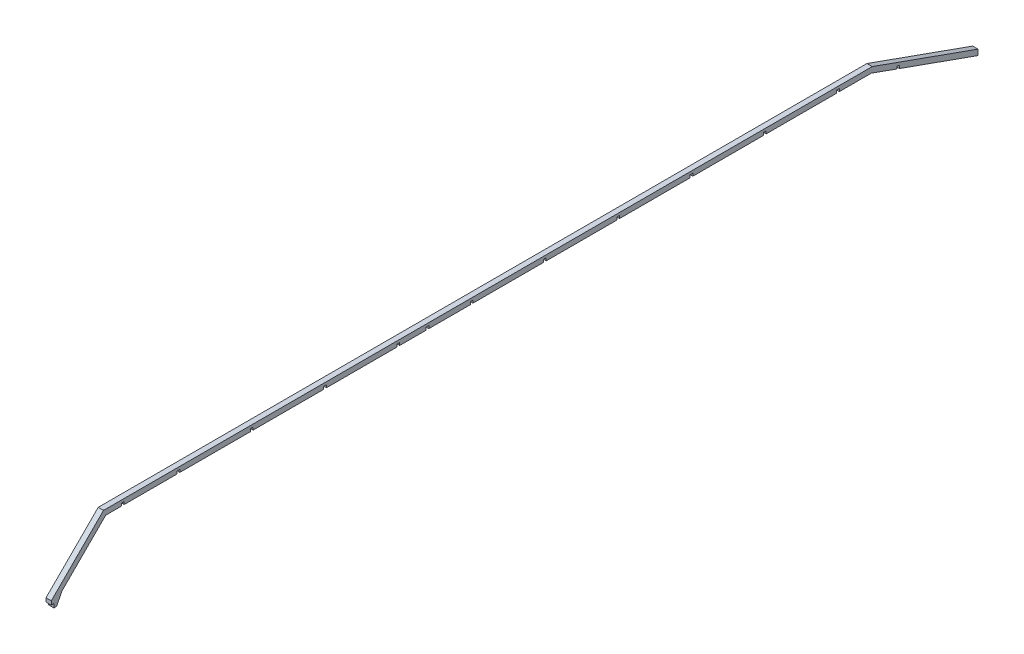
SolidWorks part; units mm, degrees
ref_plane "Спереди" through (0, 0, 0) normal (0, 0, 1) x (1, 0, 0)
ref_plane "Сверху" through (0, 0, 0) normal (0, 1, 0) x (1, 0, 0)
ref_plane "Справа" through (0, 0, 0) normal (1, 0, 0) x (0, 0, -1)
other "Configuration Table"
sketch "Эскиз1" plane through (0, 0, 0) normal (1, 0, 0) x (0, 0, -1)
  line L0 (-751.8866, -19.1422) -> (-733.9606, -19.1422)
  line L1 (115.1734, -19.1422) -> (144.0394, -29.4493)
  line L6 (160.4534, -35.3102) -> (162.4711, -29.6596) construction
  line L7 (-813.5251, -80.7807) -> (-751.8866, -19.1422) construction
  line L8 (-813.5251, -72.2954) -> (-813.5251, -80.7807) construction
  line L13 (-813.5251, -76.538) -> (-810.5251, -76.538)
  line L14 (-813.5251, -76.538) -> (-813.5251, -72.2954)
  line L17 (147.0394, -30.5205) -> (147.0394, -27.5205)
  line L18 (147.0394, -27.5205) -> (144.0394, -26.4493)
  line L19 (144.0394, -26.4493) -> (144.0394, -29.4493)
  line L20 (147.0394, -30.5205) -> (236.0394, -62.2995)
  line L21 (79.0394, -19.1422) -> (79.0394, -16.1422)
  line L22 (79.0394, -16.1422) -> (76.0394, -16.1422)
  line L23 (76.0394, -16.1422) -> (76.0394, -19.1422)
  line L24 (79.0394, -19.1422) -> (115.1734, -19.1422)
  line L25 (-3.9606, -19.1422) -> (-3.9606, -16.1422)
  line L26 (-3.9606, -16.1422) -> (-6.9606, -16.1422)
  line L27 (-6.9606, -16.1422) -> (-6.9606, -19.1422)
  line L28 (-86.9606, -19.1422) -> (-86.9606, -16.1422)
  line L29 (-86.9606, -16.1422) -> (-89.9606, -16.1422)
  line L30 (-89.9606, -16.1422) -> (-89.9606, -19.1422)
  line L31 (-169.9606, -19.1422) -> (-169.9606, -16.1422)
  line L32 (-169.9606, -16.1422) -> (-172.9606, -16.1422)
  line L33 (-172.9606, -16.1422) -> (-172.9606, -19.1422)
  line L34 (-252.9606, -19.1422) -> (-252.9606, -16.1422)
  line L35 (-252.9606, -16.1422) -> (-255.9606, -16.1422)
  line L36 (-255.9606, -16.1422) -> (-255.9606, -19.1422)
  line L37 (-335.9606, -19.1422) -> (-335.9606, -16.1422)
  line L38 (-335.9606, -16.1422) -> (-338.9606, -16.1422)
  line L39 (-338.9606, -16.1422) -> (-338.9606, -19.1422)
  line L40 (-3.9606, -19.1422) -> (76.0394, -19.1422)
  line L41 (-86.9606, -19.1422) -> (-6.9606, -19.1422)
  line L42 (-169.9606, -19.1422) -> (-89.9606, -19.1422)
  line L43 (-252.9606, -19.1422) -> (-172.9606, -19.1422)
  line L44 (-335.9606, -19.1422) -> (-255.9606, -19.1422)
  line L45 (-385.9606, -19.1422) -> (-385.9606, -16.1422)
  line L46 (-385.9606, -16.1422) -> (-388.9606, -16.1422)
  line L47 (-388.9606, -16.1422) -> (-388.9606, -19.1422)
  line L48 (-385.9606, -19.1422) -> (-338.9606, -19.1422)
  line L49 (-418.9606, -19.1422) -> (-418.9606, -16.1422)
  line L50 (-418.9606, -16.1422) -> (-421.9606, -16.1422)
  line L51 (-421.9606, -16.1422) -> (-421.9606, -19.1422)
  line L52 (-418.9606, -19.1422) -> (-388.9606, -19.1422)
  line L53 (-501.9606, -19.1422) -> (-501.9606, -16.1422)
  line L54 (-501.9606, -16.1422) -> (-504.9606, -16.1422)
  line L55 (-504.9606, -16.1422) -> (-504.9606, -19.1422)
  line L56 (-584.9606, -19.1422) -> (-584.9606, -16.1422)
  line L57 (-584.9606, -16.1422) -> (-587.9606, -16.1422)
  line L58 (-587.9606, -16.1422) -> (-587.9606, -19.1422)
  line L59 (-667.9606, -19.1422) -> (-667.9606, -16.1422)
  line L60 (-667.9606, -16.1422) -> (-670.9606, -16.1422)
  line L61 (-670.9606, -16.1422) -> (-670.9606, -19.1422)
  line L62 (-501.9606, -19.1422) -> (-421.9606, -19.1422)
  line L63 (-584.9606, -19.1422) -> (-504.9606, -19.1422)
  line L64 (-667.9606, -19.1422) -> (-587.9606, -19.1422)
  line L65 (-730.9606, -19.1422) -> (-730.9606, -16.1422)
  line L66 (-730.9606, -16.1422) -> (-733.9606, -16.1422)
  line L67 (-733.9606, -16.1422) -> (-733.9606, -19.1422)
  line L68 (-730.9606, -19.1422) -> (-670.9606, -19.1422)
  line L69 (236.0394, -62.2995) -> (238.0571, -56.6489) construction
  line L70 (-3.9606, -19.1422) -> (-3.9606, -13.1422) construction
  line L71 (162.4711, -29.6596) -> (82.2261, -1.0067) construction
  line L72 (238.0571, -56.6489) -> (162.4711, -29.6596) construction
  line L73 (79.0394, -19.1422) -> (79.0394, -13.1422) construction
  line L74 (236.0394, -62.2995) -> (236.0394, -55.9285)
  line L75 (-3.9606, -13.1422) -> (116.2125, -13.1422) construction
  line L76 (-803.8198, -71.0753) -> (-808.0624, -66.8327) construction
  line L77 (-751.8866, -19.1422) -> (-756.1293, -14.8995) construction
  line L78 (-3.9606, -13.1422) -> (-770.7331, -13.1422) construction
  line L79 (-756.1293, -14.8995) -> (-813.5251, -72.2954) construction
  line L80 (-810.5251, -76.538) -> (-810.5251, -80.7807)
  line L81 (-810.5251, -80.7807) -> (-807.5251, -80.7807)
  line L82 (-807.5251, -80.7807) -> (-801.5251, -80.7807) construction
  line L83 (-801.5251, -80.7807) -> (-801.5251, -68.7807) construction
  line L84 (-807.5251, -80.7807) -> (-801.5251, -68.7807)
  line L85 (-801.5251, -68.7807) -> (-751.8866, -19.1422)
  line L86 (-813.5251, -72.2954) -> (-754.3719, -13.1422)
  line L87 (-754.3719, -13.1422) -> (116.2125, -13.1422)
  line L88 (116.2125, -13.1422) -> (236.0394, -55.9285)
  point P49 (-388.9606, -17.6422)
  dimension "D1" = 160.35
  dimension "D2" = 128.34
  dimension "D4" = 6
  dimension "D5" = 6
  dimension "D6" = 867.06
  dimension "D7" = 6
  dimension "D8" = 3
  dimension "D9" = 3
  dimension "D10" = 6
  dimension "D11" = 81.17
  dimension "D12" = 3
  dimension "D13" = 65
  dimension "D14" = 3
  dimension "D15" = 3
  dimension "D16" = 3
  dimension "D17" = 80
  dimension "D18" = 3
  dimension "D19" = 80
  dimension "D20" = 3
  dimension "D21" = 80
  dimension "D22" = 3
  dimension "D23" = 80
  dimension "D24" = 3
  dimension "D25" = 80
  dimension "D26" = 3
  dimension "D27" = 47
  dimension "D28" = 3
  dimension "D29" = 3
  dimension "D30" = 30
  dimension "D31" = 3
  dimension "D32" = 80
  dimension "D33" = 3
  dimension "D34" = 80
  dimension "D35" = 80
  dimension "D36" = 3
  dimension "D37" = 3
  dimension "D38" = 60
  dimension "D39" = 6
  dimension "D40" = 6
extrude "Бобышка-Вытянуть3" add sketch "Эскиз1" along normal blind 6
